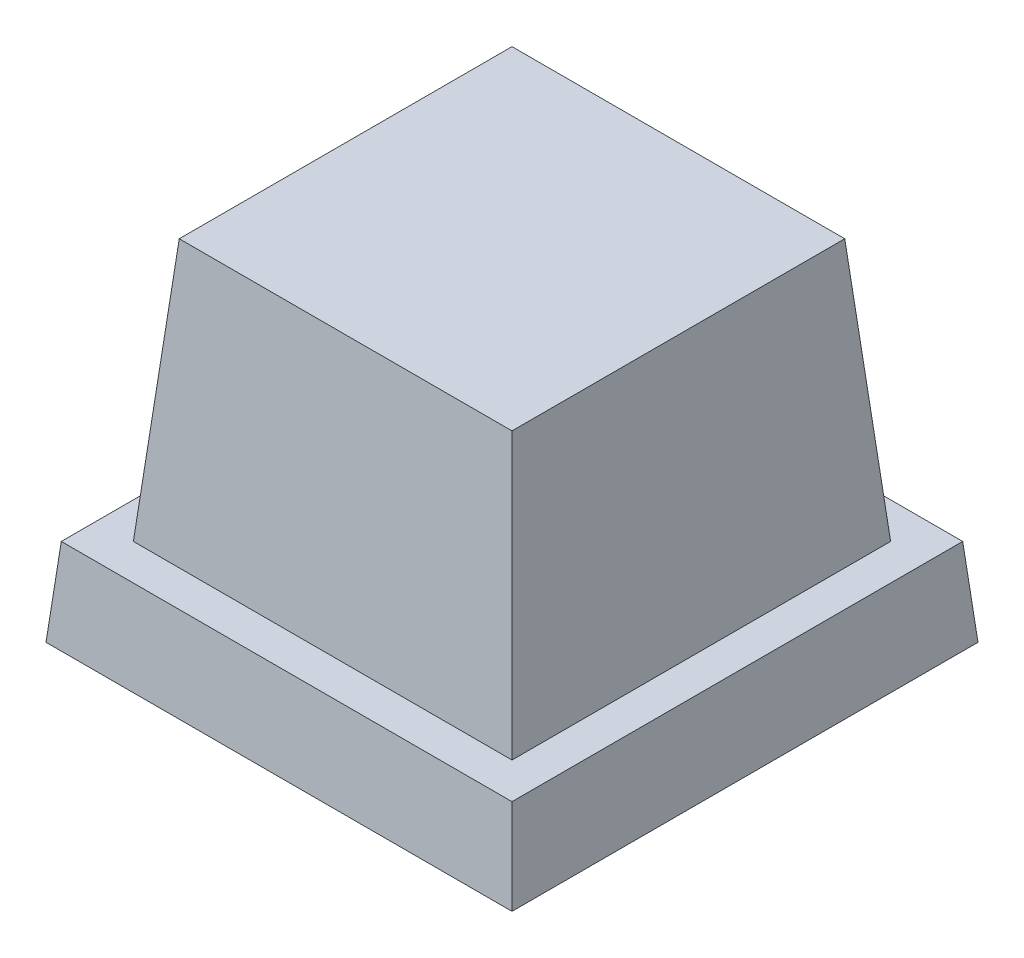
SolidWorks part; units mm, degrees
ref_plane "Front Plane" through (0, 0, 0) normal (0, 0, 1) x (1, 0, 0)
ref_plane "Top Plane" through (0, 0, 0) normal (0, 1, 0) x (1, 0, 0)
ref_plane "Right Plane" through (0, 0, 0) normal (1, 0, 0) x (0, 0, -1)
sketch "Sketch1" plane through (0, 0, 0) normal (0, 1, 0) x (1, 0, 0)
  line L13 (0, 0) -> (-32, 0)
  line L14 (0, 0) -> (0, 32)
  line L15 (0, 32) -> (-32, 32)
  line L16 (-32, 0) -> (-32, 32)
  dimension "D1" = 32
  dimension "D2" = 32
extrude "Boss-Extrude1" add sketch "Sketch1" along normal blind 6 draft 5
sketch "Sketch2" plane through (0, 6, 0) normal (0, 1, 0) x (1, 0, 0)
  line L0 (-31.4751, 0.5249) -> (-0.5249, 0.5249) construction
  line L1 (-29, 29) -> (-3, 29)
  line L2 (-29, 29) -> (-29, 3)
  line L3 (-29, 3) -> (-3, 3)
  line L4 (-3, 29) -> (-3, 3)
  line L5 (-0.5249, 0.5249) -> (-0.5249, 31.4751) construction
  point P4 (-29.5843, 29.5228)
  point P5 (-16, 3)
  point P8 (-16, 0.5249)
  point P9 (-3, 16)
  point P12 (-0.5249, 16)
  dimension "D1" = 26
  dimension "D2" = 26
extrude "Boss-Extrude2" add sketch "Sketch2" along normal blind 18 draft 5
shell "Shell1" thickness 0.8 removed face at (-16, 0, -16)
chamfer "Chamfer1" distance 2.5 angle 45 4 edges at (-16, 5.2, -1.258) (-30.742, 5.2, -16) (-16, 5.2, -30.742) (-1.258, 5.2, -16) first distance on face at (-16, 5.2, -16)
equation "\"D2@Sketch1\"=\"D1@Sketch1\""
equation "\"D2@Sketch2\"=\"D1@Sketch2\""
